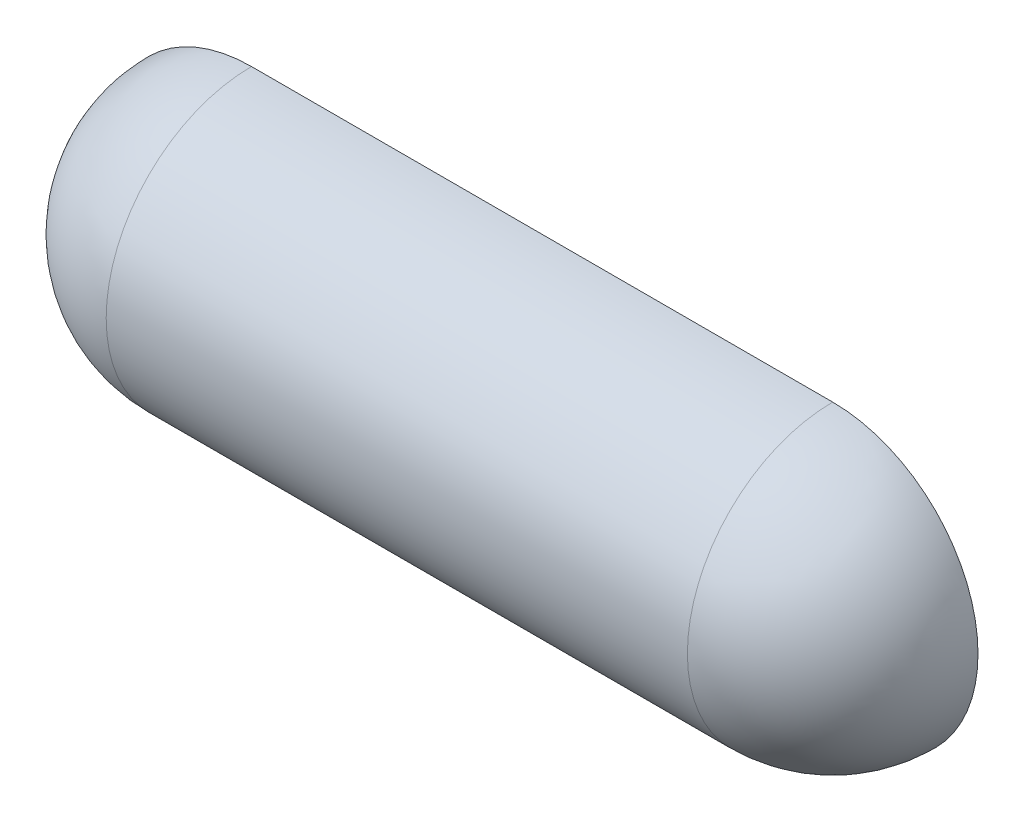
SolidWorks part; units mm, degrees
ref_plane "Front Plane" through (0, 0, 0) normal (0, 0, 1) x (1, 0, 0)
ref_plane "Top Plane" through (0, 0, 0) normal (0, 1, 0) x (1, 0, 0)
ref_plane "Right Plane" through (0, 0, 0) normal (1, 0, 0) x (0, 0, -1)
sketch "Sketch1" plane through (0, 0, 0) normal (0, 0, 1) x (1, 0, 0)
  line L0 (0, -652.3429) -> (0, 1677.7917) construction
  line L5 (-75, 0) -> (375, 0)
  line L6 (0, 75) -> (300, 75)
  line L7 (-75, -11.1998) -> (-75, 194.1976) construction
  line L8 (375, -55.0873) -> (375, 140.9739) construction
  arc A4 (0, 75) -> (-75, 0) centre (0, 0) ccw
  arc A5 (300, 75) -> (375, 0) centre (300, 0) cw
  point P13 (0, 0)
  dimension "D1" = 75
  dimension "D2" = 300
revolve "Revolve1" add sketch "Sketch1" angle 180 about L5
ref_axis "Axis1" through (0, 0, -3.75) along (0, 0, 1)
ref_plane "Plane1" through (300, 0, 0) normal (1, 0, 0) x (0, 0, -1)
ref_axis "Axis2" through (300, 0, 78.75) along (0, 0, -1)
equation "\"link2_diameter\"=150"
equation "\"link2_length\"=300"
equation "\"link3_diameter\"=150"
equation "\"link3_length\"=150"
equation "\"link4_diameter\"=150"
equation "\"link4_length\"=150"
equation "\"link5_diameter\"=150"
equation "\"link5_length\"=200"
equation "\"end_effector_diameter\"=150"
equation "\"end_effector_length\"=150"
equation "\"base_link_diameterA\"=200"
equation "\"base_link_diameterB\"=150"
equation "\"base_link_length\"=150"
equation "\"base_link_lengthA\"=50"
equation "\"link1_diameter\"=150"
equation "\"link1_length\"=150"
equation "\"D1@Sketch1\"=\"link2_diameter\"/2"
equation "\"D2@Sketch1\"=\"link2_length\""
